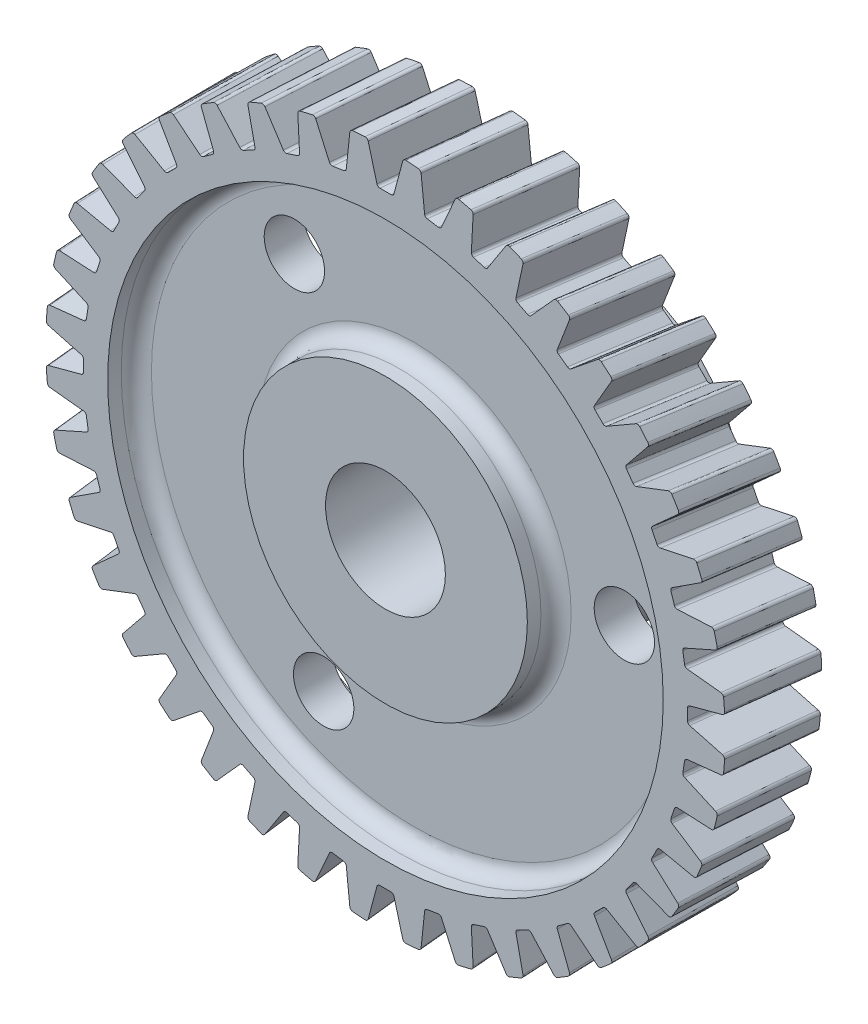
SolidWorks part; units mm, degrees
ref_plane "Front Plane" through (0, 0, 0) normal (0, 0, 1) x (1, 0, 0)
ref_plane "Top Plane" through (0, 0, 0) normal (0, 1, 0) x (1, 0, 0)
ref_plane "Right Plane" through (0, 0, 0) normal (1, 0, 0) x (0, 0, -1)
sketch "Sketch2" plane through (0, 0, 0) normal (1, 0, 0) x (0, 0, -1)
  line L0 (0, 0) -> (0, 22.5) construction
  line L1 (11, 3.9688) -> (-3.2, 3.9687)
  line L2 (-3.2, 3.9687) -> (-3.2, 9.4)
  line L3 (-3.2, 9.4) -> (-1.3, 9.4)
  line L4 (-1.3, 9.4) -> (-1.3, 18.4)
  line L5 (-1.3, 18.4) -> (-3.2, 18.4)
  line L6 (-3.2, 18.4) -> (-3.2, 22.5)
  line L7 (-3.2, 22.5) -> (3.2, 22.5)
  line L8 (3.2, 18.4) -> (3.2, 22.5)
  line L9 (1.3, 18.4) -> (3.2, 18.4)
  line L10 (1.3, 9.4) -> (1.3, 18.4)
  line L11 (3.2, 9.4) -> (1.3, 9.4)
  line L12 (3.2, 9.4) -> (11, 9.4)
  line L13 (11, 9.4) -> (11, 3.9688)
  line L14 (0, 0) -> (14.174, 0) construction
  dimension "D1" = 14.2
  dimension "D2" = 3.2
  dimension "D3" = 4.5
  dimension "D4" = 7.9375
  dimension "D5" = 9.4
  dimension "D6" = 9
  dimension "D7" = 22.5
  dimension "D8" = 6.4
revolve "Revolve1" add sketch "Sketch2" angle 360 about L14
fillet "Fillet1" radius 1 4 edges at (18.4, 0, 1.3) (9.4, 0, 1.3) (9.4, 0, -1.3) (18.4, 0, -1.3)
sketch "Sketch3" plane through (0, 0, 3.2) normal (0, 0, 1) x (1, 0, 0)
  line L0 (0, 22.6922) -> (0, 20) construction
  line L1 (-0.525, 20) -> (0.525, 20)
  line L2 (0.525, 20) -> (1.2464, 22.6922)
  line L3 (1.2464, 22.6922) -> (-1.2464, 22.6922)
  line L4 (-0.525, 20) -> (-1.2464, 22.6922)
  dimension "D1" = 20
  dimension "D2" = 1.05
  dimension "D3" = 15
sketch "Sketch4" plane through (0, 0, 0) normal (0, 1, 0) x (1, 0, 0)
  line L0 (0, -3.2) -> (0.691, 3.2)
  line L1 (1.2464, -3.2) -> (-1.2464, -3.2) construction
  line L2 (22.5, 3.2) -> (-22.5, 3.2) construction
sweep "Cut-Sweep1" cut profiles "Sketch3" path "Sketch4"
pattern_circular "CirPattern1" count 40 over 360 about axis through (0, 0, 3.2) along (0, 0, 1) of "Cut-Sweep1"
fillet "Fillet2" radius 0.2 160 edges at (1.526, 22.4482, 0.0047) (0.8705, 20, 0) (-0.8445, 22.4841, -0.0056) (-2.0045, 22.4105, 0.0047) (-2.2689, 19.8899, 0) (-3.306, 19.7257, 0) (-4.3514, 22.0752, -0.0056) (-5.4856, 21.8211, 0.0047) (-5.3525, 19.2901, 0) (-6.3511, 18.9657, 0) (-7.7512, 21.1227, -0.0056) (-8.8316, 20.6943, 0.0047) (-8.3042, 18.2153, 0) (-9.2398, 17.7386, 0) (-10.9601, 19.6501, -0.0056) (-11.9602, 19.0579, 0.0047) (-11.0515, 16.692, 0) (-11.9009, 16.0748, 0) (-13.8991, 17.6936, -0.0056) (-14.7943, 16.9523, 0.0047) (-13.5266, 14.7577, 0) (-14.2691, 14.0152, 0) (-16.4959, 15.3015, -0.0056) (-17.264, 14.4292, 0.0047) (-15.6687, 12.4599, 0) (-16.2859, 11.6105, 0) (-18.6865, 12.5326, -0.0056) (-19.3087, 11.5509, 0.0047) (-17.4249, 9.8554, 0) (-17.9016, 8.9199, 0) (-20.4169, 9.4551, -0.0056) (-20.878, 8.3882, 0.0047) (-18.7521, 7.0082, 0) (-19.0766, 6.0096, 0) (-21.6447, 6.1448, -0.0056) (-21.9331, 5.0188, 0.0047) (-19.6176, 3.9885, 0) (-19.7818, 2.9514, 0) (-22.3394, 2.6832, -0.0056) (-22.4482, 1.526, 0.0047) (-20, 0.8705, 0) (-20, -0.1795, 0) (-22.4841, -0.8445, -0.0056) (-22.4105, -2.0045, 0.0047) (-19.8899, -2.2689, 0) (-19.7257, -3.306, 0) (-22.0752, -4.3514, -0.0056) (-21.8211, -5.4856, 0.0047) (-19.2901, -5.3525, 0) (-18.9657, -6.3511, 0) (-21.1227, -7.7512, -0.0056) (-20.6943, -8.8316, 0.0047) (-18.2153, -8.3042, 0) (-17.7386, -9.2398, 0) (-19.6501, -10.9601, -0.0056) (-19.0579, -11.9602, 0.0047) (-16.692, -11.0515, 0) (-16.0748, -11.9009, 0) (-17.6936, -13.8991, -0.0056) (-16.9523, -14.7943, 0.0047) (-14.7577, -13.5266, 0) (-14.0152, -14.2691, 0) (-15.3015, -16.4959, -0.0056) (-14.4292, -17.264, 0.0047) (-12.4599, -15.6687, 0) (-11.6105, -16.2859, 0) (-12.5326, -18.6865, -0.0056) (-11.5509, -19.3087, 0.0047) (-9.8554, -17.4249, 0) (-8.9199, -17.9016, 0) (-9.4551, -20.4169, -0.0056) (-8.3882, -20.878, 0.0047) (-7.0082, -18.7521, 0) (-6.0096, -19.0766, 0) (-6.1448, -21.6447, -0.0056) (-5.0188, -21.9331, 0.0047) (-3.9885, -19.6176, 0) (-2.9514, -19.7818, 0) (-2.6832, -22.3394, -0.0056) (-1.526, -22.4482, 0.0047) (-0.8705, -20, 0) (0.1795, -20, 0) (0.8445, -22.4841, -0.0056) (2.0045, -22.4105, 0.0047) (2.2689, -19.8899, 0) (3.306, -19.7257, 0) (4.3514, -22.0752, -0.0056) (5.4856, -21.8211, 0.0047) (5.3525, -19.2901, 0) (6.3511, -18.9657, 0) (7.7512, -21.1227, -0.0056) (8.8316, -20.6943, 0.0047) (8.3042, -18.2153, 0) (9.2398, -17.7386, 0) (10.9601, -19.6501, -0.0056) (11.9602, -19.0579, 0.0047) (11.0515, -16.692, 0) (11.9009, -16.0748, 0) (13.8991, -17.6936, -0.0056) (14.7943, -16.9523, 0.0047) (13.5266, -14.7577, 0) (14.2691, -14.0152, 0) (16.4959, -15.3015, -0.0056) (17.264, -14.4292, 0.0047) (15.6687, -12.4599, 0) (16.2859, -11.6105, 0) (18.6865, -12.5326, -0.0056) (19.3087, -11.5509, 0.0047) (17.4249, -9.8554, 0) (17.9016, -8.9199, 0) (20.4169, -9.4551, -0.0056) (20.878, -8.3882, 0.0047) (18.7521, -7.0082, 0) (19.0766, -6.0096, 0) (21.6447, -6.1448, -0.0056) (21.9331, -5.0188, 0.0047) (19.6176, -3.9885, 0) (19.7818, -2.9514, 0) (22.3394, -2.6832, -0.0056) (22.4482, -1.526, 0.0047) (20, -0.8705, 0) (20, 0.1795, 0) (22.4841, 0.8445, -0.0056) (22.4105, 2.0045, 0.0047) (19.8899, 2.2689, 0) (19.7257, 3.306, 0) (22.0752, 4.3514, -0.0056) (21.8211, 5.4856, 0.0047) (19.2901, 5.3525, 0) (18.9657, 6.3511, 0) (21.1227, 7.7512, -0.0056) (20.6943, 8.8316, 0.0047) (18.2153, 8.3042, 0) (17.7386, 9.2398, 0) (19.6501, 10.9601, -0.0056) (19.0579, 11.9602, 0.0047) (16.692, 11.0515, 0) (16.0748, 11.9009, 0) (17.6936, 13.8991, -0.0056) (16.9523, 14.7943, 0.0047) (14.7577, 13.5266, 0) (14.0152, 14.2691, 0) (15.3015, 16.4959, -0.0056) (14.4292, 17.264, 0.0047) (12.4599, 15.6687, 0) (11.6105, 16.2859, 0) (12.5326, 18.6865, -0.0056) (11.5509, 19.3087, 0.0047) (9.8554, 17.4249, 0) (8.9199, 17.9016, 0) (9.4551, 20.4169, -0.0056) (8.3882, 20.878, 0.0047) (7.0082, 18.7521, 0) (6.0096, 19.0766, 0) (6.1448, 21.6447, -0.0056) (5.0188, 21.9331, 0.0047) (3.9885, 19.6176, 0) (2.9514, 19.7818, 0) (2.6832, 22.3394, -0.0056) (-0.1795, 20, 0)
ref_axis "gear axis" through (0, 0, -11) along (0, 0, 1)
hole_wizard "Ø4.0 (4) Diameter Hole1" positions "Sketch5" profile "Sketch6" hole size "Ø4.0" standard "ISO" end condition through all
sketch "Sketch5" plane through (59.759, -178.203, 3.9366) normal (0, 0, 1) x (1, -0.0054, 0)
  circle A5 centre (-60.718, 177.8786) radius 13.9687
  point P0 (-66.6414, 165.2279)
  point P2 (-68.712, 189.3338)
  point P4 (-46.8005, 179.074)
sketch "Sketch6" plane through (-5.9915, -12.6185, 3.9366) normal (1, 0, 0) x (0, -1, 0)
  line L0 (0, 0) -> (0, 14.9366)
  line L1 (0, 14.9366) -> (2, 14.9366)
  line L2 (2, 14.9366) -> (2, 0)
  line L3 (2, 0) -> (0, 0)
  line L4 (0, -6.35) -> (0, 107.95) construction
  dimension "Thru Hole Dia." = 4
  dimension "Thru Hole Depth" = 14.9366
